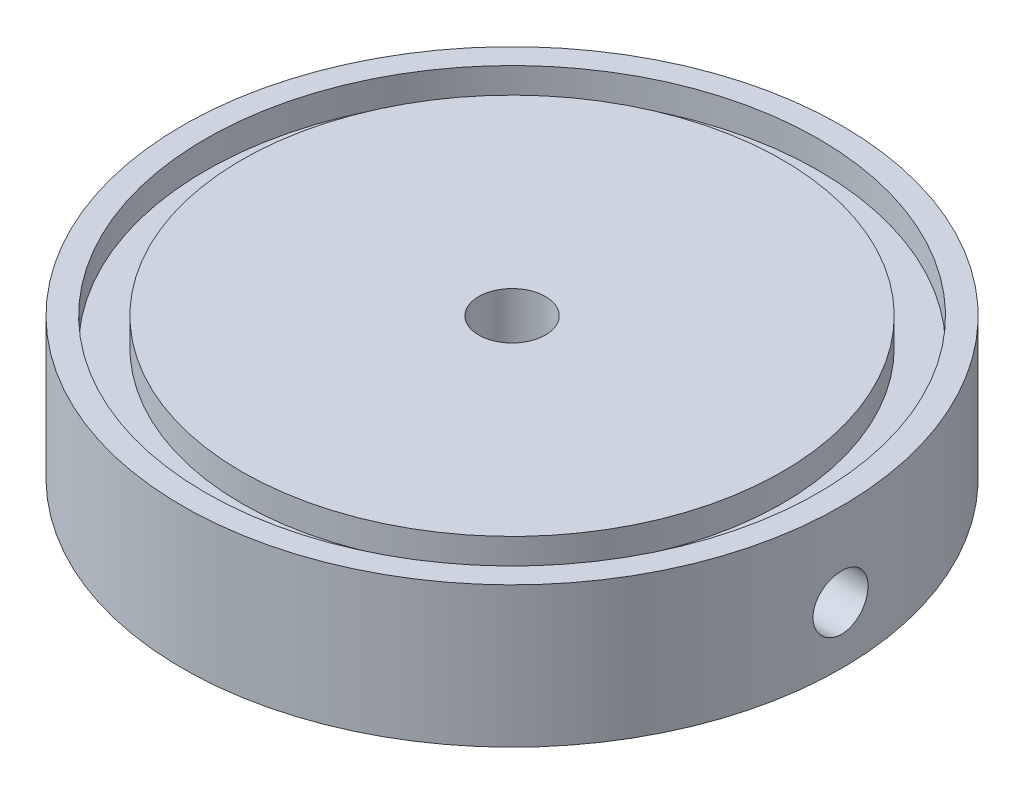
SolidWorks part; units mm, degrees
ref_plane "Front Plane" through (0, 0, 0) normal (0, 0, 1) x (1, 0, 0)
ref_plane "Top Plane" through (0, 0, 0) normal (0, 1, 0) x (1, 0, 0)
ref_plane "Right Plane" through (0, 0, 0) normal (1, 0, 0) x (0, 0, -1)
sketch "Sketch1" plane through (0, 0, 0) normal (0, 0, 1) x (1, 0, 0)
  line L0 (0, 101.6046) -> (0, 116.1639) construction
  line L1 (3.8608, 7.366) -> (38.1, 7.366)
  line L2 (3.8608, 7.366) -> (3.8608, 0)
  line L3 (10.9855, -8.89) -> (21.1455, -8.89)
  line L4 (3.8608, 0) -> (9.4615, -4.064)
  line L5 (38.1, 7.366) -> (38.1, -8.89)
  line L7 (21.1455, -8.89) -> (21.1455, -7.874)
  line L8 (21.1455, -7.874) -> (22.6695, -7.874)
  line L9 (22.6695, -7.874) -> (22.6695, -8.89)
  line L10 (22.6695, -8.89) -> (38.1, -8.89)
  line L12 (10.9855, -6.3919) -> (10.9855, -8.89)
  arc A0 (10.9855, -6.3919) -> (9.4615, -4.064) centre (8.4455, -6.3919) ccw
  dimension "D9" = 2.54
  dimension "D1" = 3.8608
  dimension "D5" = 1.524
  dimension "D6" = 1.016
  dimension "D2" = 38.1
  dimension "D4" = 7.366
  dimension "D7" = 10.9855
  dimension "D3" = 1.524
  dimension "D10" = 10.16
  dimension "D13" = 16.256
  dimension "D8" = 8.89
revolve "Revolve1" add sketch "Sketch1" angle 360 about L0
sketch "Sketch2" plane through (0, 0, 0) normal (1, 0, 0) x (0, 0, -1)
  line L0 (-38.1, -8.89) -> (38.1, -8.89) construction
  circle A0 centre (0, -2.286) radius 1.7272
  dimension "D1" = 6.604
extrude "Cut-Extrude1" cut sketch "Sketch2" along normal through all
sketch "Sketch3" plane through (0, 7.366, 0) normal (0, 1, 0) x (1, 0, 0)
  circle A0 centre (0, 0) radius 31.242
  circle A1 centre (0, 0) radius 35.433
extrude "Cut-Extrude2" cut sketch "Sketch3" against normal blind 3.175
ref_plane "Plane1" through (0, -8.89, 0) normal (0, -1, 0) x (-1, 0, 0)
sketch "Sketch4" plane through (0, -8.89, 0) normal (0, -1, 0) x (-1, 0, 0)
  line L0 (0, 0) -> (-13.97, 24.1967) construction
  circle A0 centre (-13.97, 24.1967) radius 1.0325
  circle A1 centre (0, 0) radius 27.94 construction
  dimension "D2" = 55.88
extrude "Cut-Extrude3" cut sketch "Sketch4" against normal blind 3.175
ref_axis "Axis1" through (0, 7.366, 0) along (0, -1, 0)
pattern_circular "CirPattern1" count 9 over 360 about axis through (0, 7.366, 0) along (0, -1, 0) of "Cut-Extrude3"
ref_plane "Plane2" through (38.1, 0, 0) normal (1, 0, 0) x (0, 0, -1)
ref_axis "Axis2" through (38.1, -2.286, 0) along (-1, 0, 0)
sketch "Sketch5" plane through (38.1, 0, 0) normal (1, 0, 0) x (0, 0, -1)
  circle A0 centre (0, -2.286) radius 3.175
extrude "Cut-Extrude4" cut sketch "Sketch5" against normal blind 9.525
equation "\"ManifoldChamberThickness\"= 0.35"
equation "\"AnnulusLength\"= 0.29"
equation "\"D8@Sketch1\"=\"ManifoldChamberThickness\""
equation "\"D4@Sketch1\"=\"AnnulusLength\""
